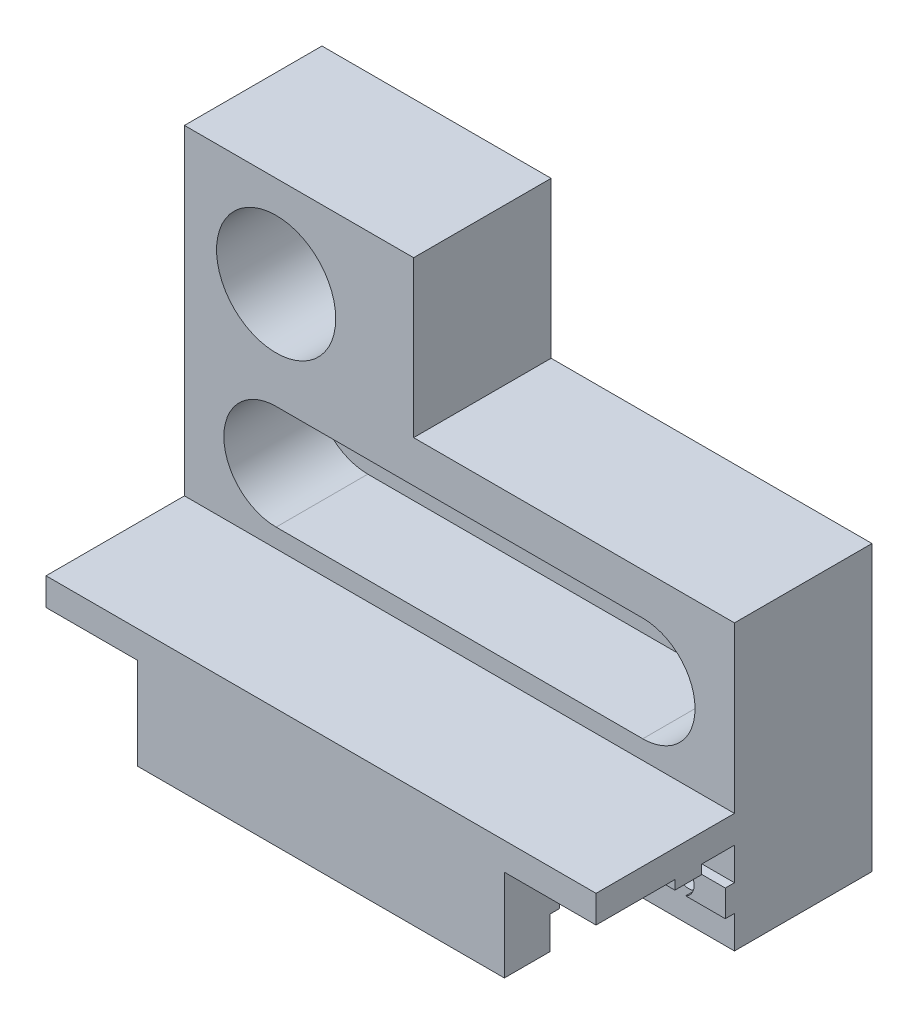
SolidWorks part; units mm, degrees
ref_plane "Front Plane" through (0, 0, 0) normal (0, 0, 1) x (1, 0, 0)
ref_plane "Top Plane" through (0, 0, 0) normal (0, 1, 0) x (1, 0, 0)
ref_plane "Right Plane" through (0, 0, 0) normal (1, 0, 0) x (0, 0, -1)
sketch "Esquisse1" plane through (0, 0, 0) normal (0, 0, 1) x (1, 0, 0)
  line L0 (-5, 17.5) -> (-5, 0.5)
  line L1 (-30, 17.5) -> (-5, 17.5)
  line L2 (-30, 17.5) -> (-30, -17.5)
  line L3 (-30, -17.5) -> (30, -17.5)
  line L4 (-5, 0.5) -> (30, 0.5)
  line L5 (30, 0.5) -> (30, -17.5)
  point P4 (-30, 0)
  point P6 (0, -17.5)
  point P7 (-9.098, 0)
  dimension "D1" = 18
  dimension "D2" = 60
  dimension "D3" = 35
  dimension "D4" = 25
extrude "Main Extrusion" add sketch "Esquisse1" along normal blind 15
sketch "Esquisse2" plane through (0, 0, 15) normal (0, 0, 1) x (1, 0, 0)
  line L0 (-20, -15.45) -> (20, -15.45)
  line L1 (20, -4.05) -> (-20, -4.05)
  line L2 (0, -55) -> (0, 55) construction
  line L4 (-30, -17.5) -> (30, -17.5) construction
  arc A0 (20, -15.45) -> (20, -4.05) centre (20, -9.75) ccw
  arc A3 (-20, -4.05) -> (-20, -15.45) centre (-20, -9.75) ccw
  point P5 (0, -4.05)
  dimension "D3" = 7.75
  dimension "D1" = 40
  dimension "D2" = 5.7
extrude "Double Circle" cut sketch "Esquisse2" against normal blind 10
sketch "Esquisse5" plane through (0, 0, 15) normal (0, 0, 1) x (1, 0, 0)
  line L1 (-30, -17.5) -> (30, -17.5) construction
  line L3 (-30, 17.5) -> (-30, -17.5) construction
  circle A0 centre (-20, 7.5) radius 1.6
  dimension "D1" = 3.2
  dimension "D2" = 25
  dimension "D3" = 10
extrude "Gear Linear Holes" cut sketch "Esquisse5" against normal through all
ref_plane "Plan1" through (15, 0, 0) normal (1, 0, 0) x (0, 0, -1)
ref_axis "Axe1" through (15, 0, -1.355) along (0, 0, 1)
sketch "Esquisse8" plane through (0, 0, 0) normal (1, 0, 0) x (0, 0, -1)
  line L0 (-15, -20.5) -> (-15, -24.05)
  line L1 (-15, -20.5) -> (-18.6, -20.5)
  line L2 (-18.6, -20.5) -> (-18.6, -21.5)
  line L3 (-18.6, -21.5) -> (-21.5, -21.5)
  line L4 (-21.5, -21.5) -> (-21.5, -20.5)
  line L5 (-30.1, -17.5) -> (0, -17.5)
  line L6 (-15, -30.5) -> (0, -30.5)
  line L7 (0, -30.5) -> (0, -17.5)
  line L8 (-15, -17.5) -> (-15, 0.5) construction
  line L9 (-21.5, -20.5) -> (-25.1, -20.5)
  line L10 (0, -17.5) -> (0, 0.5) construction
  line L11 (-15, -17.5) -> (0, -17.5) construction
  line L13 (-25.1, -20.5) -> (-25.1, -24.05)
  line L14 (-25.1, -30.5) -> (-30.1, -30.5)
  line L15 (-30.1, -30.5) -> (-30.1, -17.5)
  line L16 (-15, -24.05) -> (-16, -24.05)
  line L17 (-16, -24.05) -> (-16, -26.95)
  line L18 (-16, -26.95) -> (-15, -26.95)
  line L19 (-15, -26.95) -> (-15, -30.5)
  line L21 (-25.1, -24.05) -> (-24.1, -24.05)
  line L22 (-24.1, -24.05) -> (-24.1, -26.95)
  line L23 (-24.1, -26.95) -> (-25.1, -26.95)
  line L24 (-25.1, -26.95) -> (-25.1, -30.5)
  point P12 (-17.324, -31.1687)
  point P21 (0, 0)
  point P26 (-26.4545, -30.5)
  dimension "D1" = 2.9
  dimension "D2" = 10.1
  dimension "D3" = 1
  dimension "D4" = 3
  dimension "D5" = 10
  dimension "D6" = 5
extrude "Fixing Extrusion" add sketch "Esquisse8" along normal mid plane 60
sketch "Esquisse10" plane through (0, 0, 0) normal (0, 0, -1) x (-1, 0, 0)
  line L0 (30, -30.5) -> (30, 17.5) construction
  line L1 (-30, -30.5) -> (-30, 0.5) construction
  line L2 (-30, -30.5) -> (30, -30.5) construction
  circle A0 centre (-25, -25.5) radius 1.6
  circle A1 centre (25, -25.5) radius 1.6
  dimension "D2" = 3.2
  dimension "D1" = 5
  dimension "D3" = 5
  dimension "D4" = 5
extrude "Enlèv. mat.-Extru.3" cut sketch "Esquisse10" against normal through all
sketch "Esquisse11" plane through (0, 0, 30.1) normal (0, 0, 1) x (1, 0, 0)
  line L1 (-30, -30.5) -> (-20, -30.5)
  line L2 (-30, -30.5) -> (-30, -20.5)
  line L3 (-30, -20.5) -> (-20, -20.5)
  line L4 (-20, -30.5) -> (-20, -20.5)
  line L5 (20, -20.5) -> (30, -20.5)
  line L6 (20, -20.5) -> (20, -30.5)
  line L7 (20, -30.5) -> (30, -30.5)
  line L8 (30, -20.5) -> (30, -30.5)
  dimension "D1" = 10
extrude "Enlèv. mat.-Extru.4" cut sketch "Esquisse11" against normal up to surface (6 mm away) up to face at (0, -25.5, 24.1)
sketch "Esquisse12" plane through (0, 0, 15) normal (0, 0, 1) x (1, 0, 0)
  circle A0 centre (-20, 7.5) radius 6.5
  dimension "D1" = 13
extrude "Enlèv. mat.-Extru.5" cut sketch "Esquisse12" against normal up to surface (10 mm away) up to face at (0, -9.75, 5)
